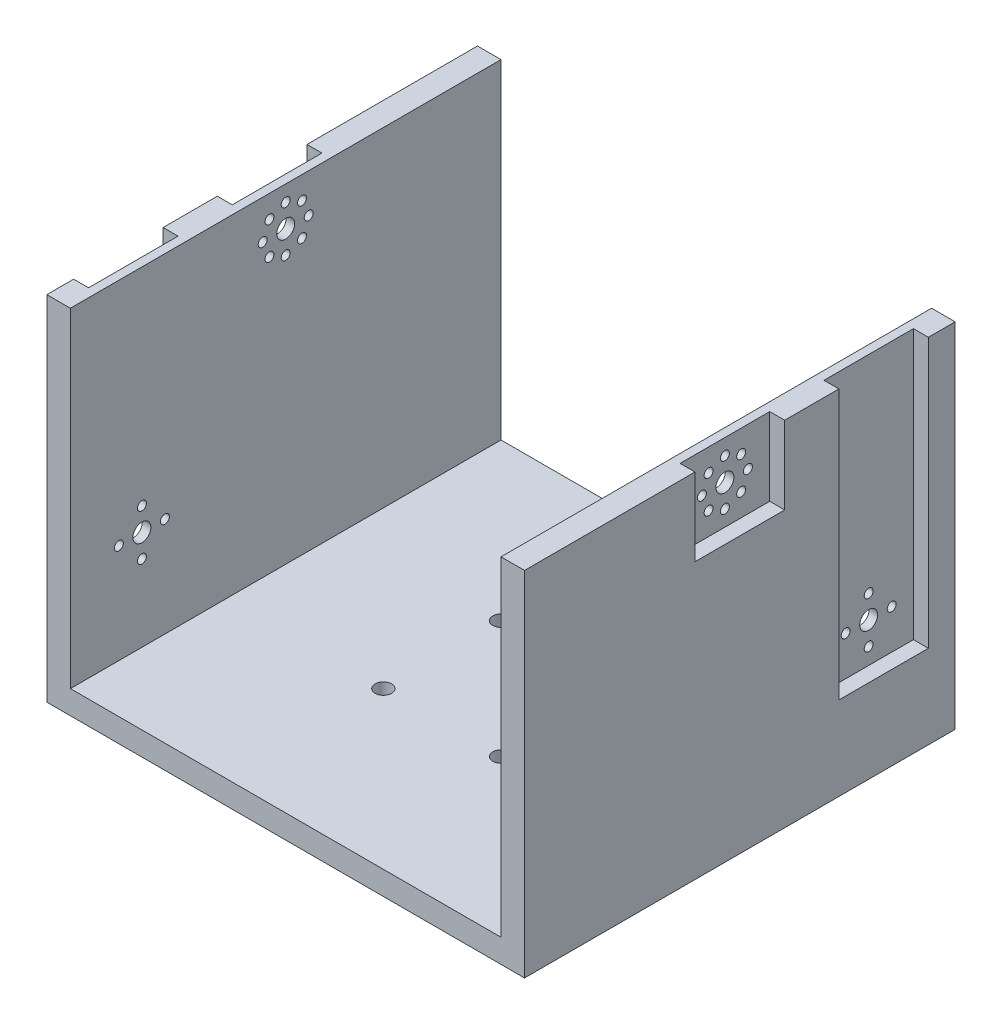
SolidWorks part; units mm, degrees
ref_plane "Front" through (0, 0, 0) normal (0, 0, 1) x (1, 0, 0)
ref_plane "Top" through (0, 0, 0) normal (0, 1, 0) x (1, 0, 0)
ref_plane "Right" through (0, 0, 0) normal (1, 0, 0) x (0, 0, -1)
sketch "Sketch2" plane through (0, 0, 0) normal (0, 1, 0) x (1, 0, 0)
  line L0 (0, 0) -> (0, -91.5) construction
  line L1 (-91.5, -91.5) -> (91.5, -91.5)
  line L2 (-91.5, -91.5) -> (-91.5, 91.5)
  line L3 (-91.5, 91.5) -> (91.5, 91.5)
  line L4 (91.5, -91.5) -> (91.5, 91.5)
  line L5 (0, 0) -> (-91.5, 0) construction
  point P0 (0, 0)
  dimension "D1" = 183
  dimension "D2" = 183
extrude "Boss-Extrude1" add sketch "Sketch2" along normal blind 10
sketch "Sketch3" plane through (0, 0, 0) normal (0, 1, 0) x (1, 0, 0)
  line L0 (-91.5, -91.5) -> (91.5, -91.5) construction
  line L1 (-91.5, 91.5) -> (-101.5, 91.5)
  line L2 (-91.5, 91.5) -> (-91.5, -91.5)
  line L3 (-91.5, -91.5) -> (-101.5, -91.5)
  line L4 (-101.5, 91.5) -> (-101.5, -91.5)
  line L5 (0, 0) -> (0, 91.5) construction
  line L6 (91.5, 91.5) -> (-91.5, 91.5) construction
  line L7 (101.5, 91.5) -> (101.5, -91.5)
  line L8 (91.5, -91.5) -> (101.5, -91.5)
  line L9 (91.5, 91.5) -> (91.5, -91.5)
  line L10 (91.5, 91.5) -> (101.5, 91.5)
  dimension "D1" = 10
extrude "Boss-Extrude2" add sketch "Sketch3" along normal blind 150
sketch "Sketch4" plane through (0, 10, 0) normal (0, 1, 0) x (1, 0, 0)
  point P4 (0, 0)
hole_wizard "M6 Clearance Hole1" positions "Sketch5" profile "Sketch6" hole size "M6" standard "ANSI Metric" end condition up to next
sketch "Sketch5" plane through (0, 10, 0) normal (0, 1, 0) x (1, 0, 0)
  line L0 (0, 0) -> (0, 25) construction
  line L1 (0, 25) -> (-25, 25) construction
  line L3 (0, 25) -> (25, 25) construction
  point P0 (-25, 25)
  point P13 (25, 25)
  point P14 (25, -25)
  point P15 (-25, -25)
  dimension "D1" = 25
  dimension "D2" = 4
sketch "Sketch6" plane through (-25, 10, -25) normal (1, 0, 0) x (0, 0, 1)
  line L0 (0, 0) -> (0, 10)
  line L1 (0, 10) -> (3.5, 10)
  line L2 (3.5, 10) -> (3.5, 0)
  line L5 (3.5, 0) -> (0, 0)
  line L11 (0, -6.35) -> (0, 107.95) construction
  dimension "Thru Hole Dia." = 7
  dimension "Thru Hole Depth" = 10
sketch "Sketch7" plane through (91.5, 0, 0) normal (-1, 0, 0) x (0, 0, 1)
  line L0 (-91.5, 150) -> (91.5, 150) construction
  line L1 (0, 133.49) -> (0, 143.269) construction
  line L2 (0, 133.49) -> (0, 143.269) construction
  circle A0 centre (0, 133.49) radius 3.81
  circle A1 centre (0, 143.269) radius 1.8987
  circle A2 centre (6.9148, 140.4048) radius 1.8987
  circle A3 centre (9.779, 133.49) radius 1.8987
  circle A4 centre (6.9148, 126.5752) radius 1.8987
  circle A5 centre (0, 123.711) radius 1.8987
  circle A6 centre (-6.9148, 126.5752) radius 1.8987
  circle A7 centre (-9.779, 133.49) radius 1.8987
  circle A8 centre (-6.9148, 140.4048) radius 1.8987
  point P7 (0, 150)
  dimension "D1" = 7.62
  dimension "D3" = 3.7973
  dimension "D2" = 16.51
  dimension "D6" = 9.779
  dimension "D5" = 8
extrude "Cut-Extrude1" cut sketch "Sketch7" against normal through all both and the other way through all
sketch "Sketch8" plane through (0, 150, 0) normal (0, 1, 0) x (1, 0, 0)
  line L1 (95.15, -19.05) -> (101.5, -19.05)
  line L2 (95.15, -19.05) -> (95.15, 19.05)
  line L3 (95.15, 19.05) -> (101.5, 19.05)
  line L4 (101.5, -19.05) -> (101.5, 19.05)
  line L5 (95.15, -19.05) -> (101.5, 19.05) construction
  line L6 (95.15, 19.05) -> (101.5, -19.05) construction
  line L9 (101.5, -91.5) -> (101.5, 91.5) construction
  line L10 (0, 0) -> (0, 91.5) construction
  line L11 (91.5, 91.5) -> (-91.5, 91.5) construction
  line L13 (-95.15, 19.05) -> (-101.5, -19.05) construction
  line L14 (-95.15, -19.05) -> (-101.5, 19.05) construction
  line L16 (-101.5, -19.05) -> (-101.5, 19.05)
  line L17 (-95.15, 19.05) -> (-101.5, 19.05)
  line L18 (-95.15, -19.05) -> (-95.15, 19.05)
  line L19 (-95.15, -19.05) -> (-101.5, -19.05)
  point P0 (98.325, 0)
  point P12 (101.5, 0)
  point P23 (-98.325, 0)
  dimension "D1" = 38.1
  dimension "D2" = 6.35
extrude "Cut-Extrude2" cut sketch "Sketch8" against normal blind 33.02
sketch "Sketch9" plane through (101.5, 0, 0) normal (1, 0, 0) x (0, 0, -1)
  line L0 (44.5889, 35.5504) -> (50.6849, 35.5504) construction
  line L2 (80.1089, 69.0884) -> (80.1089, 35.5404)
  line L3 (80.1089, 35.5404) -> (42.0889, 35.5404)
  line L4 (42.0889, 69.0884) -> (42.0889, 35.5404)
  line L5 (80.1089, 69.0884) -> (42.0889, 35.5404) construction
  line L6 (80.1089, 35.5404) -> (42.0889, 69.0884) construction
  line L7 (44.5889, 44.6944) -> (44.5889, 35.5504) construction
  line L13 (80.1089, 69.0884) -> (80.1089, 150)
  line L14 (19.05, 150) -> (91.5, 150) construction
  line L15 (80.1089, 150) -> (42.0889, 150)
  line L16 (42.0889, 150) -> (42.0889, 69.0884)
  point P0 (61.0989, 52.3144)
  point P10 (61.0989, 62.0934)
  point P11 (51.3199, 52.3144)
  point P13 (61.0989, 42.5354)
  point P15 (70.8779, 52.3144)
  dimension "D1" = 0.01
  dimension "D2" = 2.5
extrude "Cut-Extrude3" cut sketch "Sketch9" against normal blind 6.35
sketch "Sketch11" plane through (95.15, 0, 0) normal (1, 0, 0) x (0, 0, -1)
  circle A0 centre (61.0989, 52.3144) radius 3.81
  circle A1 centre (0, 133.49) radius 3.81 construction
extrude "Cut-Extrude4" cut sketch "Sketch11" against normal up to next
hole_wizard "#6 Clearance Hole1" positions "Sketch12" profile "Sketch13" hole size "#6" standard "ANSI Inch" end condition up to next
sketch "Sketch12" plane through (95.15, 0, 0) normal (1, 0, 0) x (0, 0, -1)
  point P0 (61.0989, 62.0934)
  point P3 (51.3199, 52.3144)
  point P6 (70.8779, 52.3144)
  point P10 (61.0989, 42.5354)
sketch "Sketch13" plane through (95.15, 62.0934, -61.0989) normal (0, 1, 0) x (0, 0, -1)
  line L0 (0, 0) -> (0, 3.65)
  line L1 (0, 3.65) -> (1.8986, 3.65)
  line L2 (1.8986, 3.65) -> (1.8986, 0)
  line L5 (1.8986, 0) -> (0, 0)
  line L11 (0, -6.35) -> (0, 107.95) construction
  dimension "Thru Hole Dia." = 3.7973
  dimension "Thru Hole Depth" = 3.65
ref_plane "Plane1" through (0, 0, 0) normal (-0.7071, 0, 0.7071) x (0.7071, 0, 0.7071)
ref_axis "Axis1" through (0, 0, 0) along (0, 1, 0)
pattern_circular "CirPattern1" count 2 over 360 about axis through (0, 0, 0) along (0, 1, 0) of "Cut-Extrude3", "Cut-Extrude4", "#6 Clearance Hole1"
equation "\"Longueur\" = 183"
equation "\"D2@Sketch2\"=\"Longueur\""
equation "\"Largeur\"= 183"
equation "\"D1@Sketch2\"=\"Largeur\""
